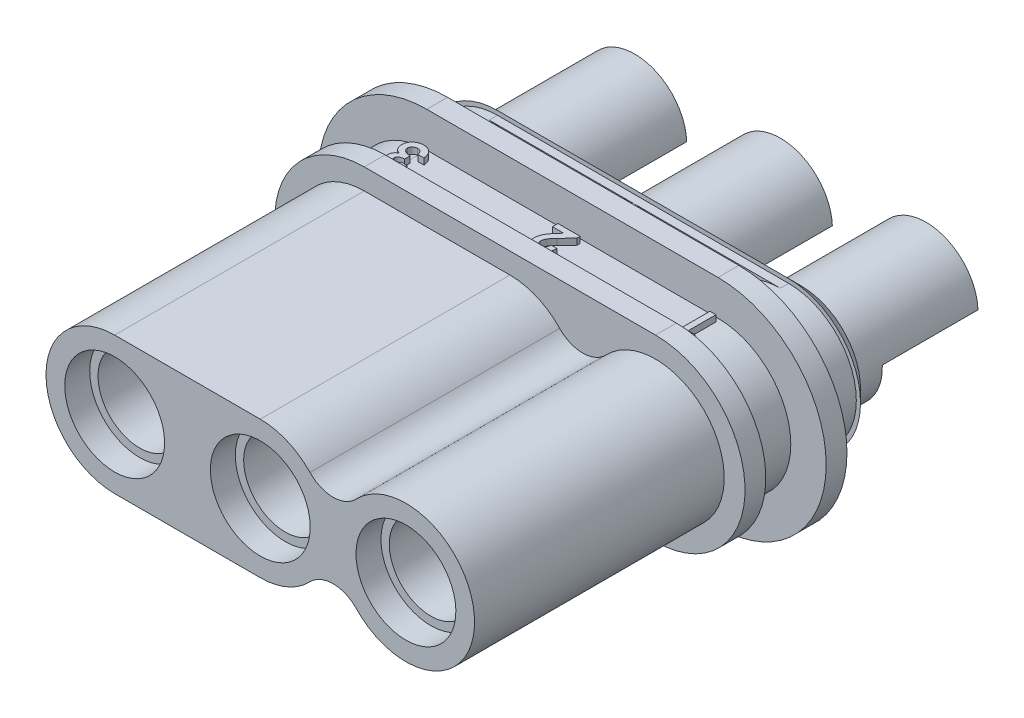
SolidWorks part; units mm, degrees
material "PA Type 6"
ref_plane "Front" through (0, 0, 0) normal (0, 0, 1) x (1, 0, 0)
ref_plane "Top" through (0, 0, 0) normal (0, 1, 0) x (1, 0, 0)
ref_plane "Side" through (0, 0, 0) normal (1, 0, 0) x (0, 0, -1)
ref_axis "Axis1" through (0, 0, 54.75) along (0, 0, -1)
sketch "Sketch1" plane through (0, 0, 0) normal (0, 0, 1) x (1, 0, 0)
  line L0 (-3.5, 0) -> (3.5, 0) construction
  line L1 (6.05, 0) -> (-6.05, 0) construction
  line L2 (-3.5, 1.65) -> (3.5, 1.65)
  line L3 (-3.5, -1.65) -> (3.5, -1.65)
  arc A0 (-3.5, 1.65) -> (-3.5, -1.65) centre (-3.5, 0) ccw
  arc A1 (3.5, -1.65) -> (3.5, 1.65) centre (3.5, 0) ccw
  point P5 (0, 0)
  dimension "D2" = 7
  dimension "D1" = 3.3
extrude "Boss-Extrude1" add sketch "Sketch1" along normal blind 6
sketch "Sketch2" plane through (0, 0, 0) normal (0, 0, 1) x (1, 0, 0)
  circle A0 centre (3.5, 0) radius 1.25
  circle A1 centre (0, 0) radius 1.25
  circle A2 centre (-3.5, 0) radius 1.25
  dimension "D1" = 2.5
sketch "Sketch3" plane through (0, 0, 6) normal (0, 0, 1) x (1, 0, 0)
  line L0 (3.5, 1.65) -> (-3.5, 1.65) construction
  line L1 (3.5, 1.65) -> (0, 1.65)
  line L2 (3.3, 0) -> (-3.3, 0) construction
  line L3 (0, 0) -> (7.6068, 0) construction
  line L4 (3.5, -1.65) -> (0, -1.65)
  arc A0 (3.5, 1.65) -> (2.3052, 1.1379) centre (3.5, 0) ccw
  arc A2 (1.1948, 1.1379) -> (0, 1.65) centre (0, 0) ccw
  arc A3 (1.1948, 1.1379) -> (2.3052, 1.1379) centre (1.75, 1.6667) ccw
  arc A4 (1.1948, -1.1379) -> (2.3052, -1.1379) centre (1.75, -1.6667) cw
  arc A5 (1.1948, -1.1379) -> (0, -1.65) centre (0, 0) cw
  arc A6 (3.5, -1.65) -> (2.3052, -1.1379) centre (3.5, 0) cw
  arc A7 (3.5, -1.65) -> (3.5, 1.65) centre (3.5, 0) ccw construction
  dimension "D1" = 0.7667
  dimension "D2" = 0.9
extrude "Cut-Extrude7" cut sketch "Sketch3" against normal through all
sketch "Sketch25" plane through (0, 0, 0) normal (0, 0, -1) x (-1, 0, 0)
  line L0 (-3.5, 0) -> (3.5, 0) construction
  line L1 (-3.5, 2.15) -> (3.5, 2.15)
  line L2 (-3.5, -2.15) -> (3.5, -2.15)
  arc A0 (-3.5, 2.15) -> (-3.5, -2.15) centre (-3.5, 0) ccw
  arc A1 (3.5, -2.15) -> (3.5, 2.15) centre (3.5, 0) ccw
  point P2 (0, 0)
  dimension "D1" = 4.3
extrude "Boss-Extrude14" add sketch "Sketch25" along normal blind 0.5
sketch "Sketch26" plane through (0, 0, -0.5) normal (0, 0, -1) x (-1, 0, 0)
  line L0 (-3.5, 0) -> (3.5, 0) construction
  line L1 (-3.5, 1.75) -> (3.5, 1.75)
  line L2 (-3.5, -1.75) -> (3.5, -1.75)
  arc A0 (-3.5, 1.75) -> (-3.5, -1.75) centre (-3.5, 0) ccw
  arc A1 (3.5, -1.75) -> (3.5, 1.75) centre (3.5, 0) ccw
  point P2 (0, 0)
  dimension "D1" = 3.5
extrude "Boss-Extrude15" add sketch "Sketch26" along normal blind 1
sketch "Sketch27" plane through (0, 0, -1.5) normal (0, 0, -1) x (-1, 0, 0)
  line L0 (-3.5, 0) -> (3.5, 0) construction
  line L1 (-3.5, 2.6) -> (3.5, 2.6)
  line L2 (-3.5, -2.6) -> (3.5, -2.6)
  arc A0 (-3.5, 2.6) -> (-3.5, -2.6) centre (-3.5, 0) ccw
  arc A1 (3.5, -2.6) -> (3.5, 2.6) centre (3.5, 0) ccw
  point P2 (0, 0)
  dimension "D1" = 5.2
extrude "Boss-Extrude16" add sketch "Sketch27" along normal blind 0.5
sketch "Sketch28" plane through (0, 0, -2) normal (0, 0, -1) x (-1, 0, 0)
  line L0 (-3.5, 0) -> (3.5, 0) construction
  line L1 (-3.5, 1.725) -> (3.5, 1.725)
  line L2 (-3.5, -1.725) -> (3.5, -1.725)
  arc A0 (-3.5, 1.725) -> (-3.5, -1.725) centre (-3.5, 0) ccw
  arc A1 (3.5, -1.725) -> (3.5, 1.725) centre (3.5, 0) ccw
  point P2 (0, 0)
  dimension "D1" = 3.45
extrude "Boss-Extrude17" add sketch "Sketch28" along normal blind 1.5
chamfer "Chamfer2" distance 0.3 angle 45 4 edges at (0, 1.725, -3.5) (-5.225, 0, -3.5) (0, -1.725, -3.5) (5.225, 0, -3.5)
sketch "Sketch29" plane through (0, 0, -2) normal (0, 0, -1) x (-1, 0, 0)
  line L4 (3.5, 1.625) -> (-3.5, 1.625)
  line L5 (-3.5, -1.625) -> (3.5, -1.625)
  line L6 (3.5, 1.625) -> (-3.5, 1.625)
  line L7 (-3.5, -1.625) -> (3.5, -1.625)
  line L8 (3.5, 1.725) -> (-3.5, 1.725)
  line L9 (-3.5, -1.725) -> (3.5, -1.725)
  line L10 (3.5, 1.725) -> (-3.5, 1.725)
  line L11 (-3.5, -1.725) -> (3.5, -1.725)
  arc A4 (3.5, -1.625) -> (3.5, 1.625) centre (3.5, 0) ccw
  arc A5 (-3.5, 1.625) -> (-3.5, -1.625) centre (-3.5, 0) ccw
  arc A6 (3.5, -1.625) -> (3.5, 1.625) centre (3.5, 0) ccw
  arc A7 (-3.5, 1.625) -> (-3.5, -1.625) centre (-3.5, 0) ccw
  arc A8 (3.5, -1.725) -> (3.5, 1.725) centre (3.5, 0) ccw
  arc A9 (-3.5, 1.725) -> (-3.5, -1.725) centre (-3.5, 0) ccw
  arc A10 (3.5, -1.725) -> (3.5, 1.725) centre (3.5, 0) ccw
  arc A11 (-3.5, 1.725) -> (-3.5, -1.725) centre (-3.5, 0) ccw
  dimension "D3" = 3.25
  dimension "D1" = 0.1
  dimension "D2" = 0
extrude "Cut-Extrude9" cut sketch "Sketch29" along normal up to vertex up to point (3.5, -1.725, -3.2)
sketch "Sketch35" plane through (0, 0, -2) normal (0, 0, -1) x (-1, 0, 0)
  line L5 (3.5, 1.625) -> (3.5, 2.6)
  line L10 (0, 1.625) -> (0, 2.6)
  line L11 (0, 2.6) -> (3.5, 2.6)
  line L12 (5.225, 0) -> (-5.225, 0) construction
  line L13 (3.5, 2.6) -> (-3.5, 2.6) construction
  circle A4 centre (3.5, 0) radius 1.25 construction
  circle A5 centre (0, 0) radius 1.25 construction
  arc A10 (1.2535, 1.034) -> (0, 1.625) centre (0, 0) ccw
  arc A11 (2.2465, 1.034) -> (1.2535, 1.034) centre (1.75, 1.4436) cw
  arc A12 (3.5, 1.625) -> (2.2465, 1.034) centre (3.5, 0) ccw
  arc A13 (3.5, -1.625) -> (3.5, 1.625) centre (3.5, 0) ccw construction
  dimension "D1" = 0.8
extrude "Cut-Extrude11" cut sketch "Sketch35" along normal offset from surface (1 mm away) 0.2 up to face at (0, 0, -3.2)
mirror "Mirror4" about plane through (0, 0, 0) normal (1, 0, 0) of "Cut-Extrude11"
mirror "Mirror5" about plane through (0, 0, 0) normal (0, 1, 0) of "Cut-Extrude11", "Mirror4"
ref_plane "Plane2" through (3.5, 0, 0) normal (1, 0, 0) x (0, 0, -1)
sketch "Sketch31" plane through (3.5, 0, 0) normal (1, 0, 0) x (0, 0, -1)
  line L0 (0, 0) -> (-7.12, 0) construction
  line L1 (0, 0) -> (3.5, 0) construction
  line L2 (-6, 0) -> (-6, 1.2)
  line L3 (-6, 1.65) -> (-6, -1.65) construction
  line L4 (-6, 1.2) -> (0.5, 1.2)
  line L5 (0.5, 1.2) -> (0.5, 1.25)
  line L6 (0.5, -1.75) -> (0.5, 1.75) construction
  line L7 (0.5, 1.25) -> (3.5, 1.25)
  line L8 (3.5, 1.25) -> (3.5, 0)
  line L9 (3.5, -1.425) -> (3.5, 1.425) construction
  line L10 (-6, 0) -> (3.5, 0)
  dimension "D3" = 2.5
  dimension "D1" = 6.5
  dimension "D2" = 2.4
revolve "Cut-Revolve1" cut sketch "Sketch31" angle 360 about L10
pattern_linear "LPattern4" count 3 spacing 3.5 along (-1, 0, 0) of "Cut-Revolve1"
sketch "Sketch32" plane through (3.5, 0, 0) normal (1, 0, 0) x (0, 0, -1)
  line L0 (-5.4, 1.2) -> (-5.4, 1)
  line L1 (-5.4, 1) -> (1.1, 1)
  line L3 (0.5, 1.2) -> (-6, 1.2) construction
  line L4 (0.5, 1.2) -> (-5.4, 1.2)
  line L5 (0, 0) -> (-6.3597, 0) construction
  line L6 (-6, 1.65) -> (-6, -1.65) construction
  line L8 (0.5, -1.25) -> (0.5, 1.25) construction
  line L9 (0.5, 1.2) -> (0.5, 1.25)
  line L10 (0.5, 1.25) -> (6.5, 1.25)
  line L12 (6.5, 1.25) -> (6.5, 0.7)
  line L13 (3.5, -1.425) -> (3.5, 1.425) construction
  line L14 (6.5, 0.7) -> (2.8, 0.7)
  line L15 (2.8, 0.7) -> (2.3794, 0)
  line L16 (1.7009, 0) -> (2.3794, 0)
  line L17 (1.1, 1) -> (1.7009, 0)
  dimension "D1" = 2
  dimension "D2" = 0.6
  dimension "D3" = 3
  dimension "D4" = 1.4
  dimension "D5" = 59
  dimension "D6" = 3.7
  dimension "D7" = 6.5
  dimension "D8" = 59
revolve "Revolve1" add sketch "Sketch32" angle 360 about L5
sketch "Sketch33" plane through (0, 0, 0) normal (1, 0, 0) x (0, 0, -1)
  line L0 (6.5, -1.25) -> (6.5, 1.25) construction
  line L1 (6.5, 0.05) -> (4.2, 0.05)
  line L2 (6.5, 0.05) -> (6.5, -1.25)
  line L3 (6.5, -1.25) -> (4.2, -1.25)
  line L4 (4.2, 0.05) -> (4.2, -1.25)
  line L5 (6.5, 1.25) -> (0.5, 1.25) construction
  dimension "D1" = 2.3
  dimension "D2" = 1.2
extrude "Cut-Extrude10" cut sketch "Sketch33" against normal through all both and the other way through all
pattern_linear "LPattern5" count 3 spacing 3.5 along (-1, 0, 0) of bodies 158
ref_plane "Plane3" through (0, 1.9, 0) normal (0, 1, 0) x (1, 0, 0)
sketch "Sketch38" plane through (0, 1.9, 0) normal (0, 1, 0) x (1, 0, 0)
  line L0 (-4.2497, 1.4) -> (-2.7503, 1.4) construction
  line L2 (-3.5, 1.5) -> (3.5, 1.5) construction
  line L4 (-0.9888, 1.4) -> (0.9888, 1.4) construction
  line L5 (2.4642, 1.4) -> (4.5358, 1.4) construction
  text T0 "1"
  text T1 "2"
  text T2 "3"
  dimension "D1" = 0.1
extrude "Boss-Extrude18" add sketch "Sketch38" against normal blind 0.3
ref_plane "Plane4" through (0, -1.9, 0) normal (0, -1, 0) x (-1, 0, 0)
sketch "Sketch39" plane through (0, -1.9, 0) normal (0, -1, 0) x (-1, 0, 0)
  line L0 (-4.0045, 1.4) -> (-2.9955, 1.4) construction
  line L1 (-0.8219, 1.4) -> (0.8219, 1.4) construction
  line L2 (3.0253, 1.4) -> (3.9747, 1.4) construction
  line L4 (0, 2.86) -> (0, -2.86) construction
  line L7 (-3.5, 1.5) -> (3.5, 1.5) construction
  text T0 "3"
  text T1 "2"
  text T2 "1"
  point P9 (0, 1.4)
  dimension "D1" = 0.1
extrude "Boss-Extrude19" add sketch "Sketch39" against normal blind 0.3
